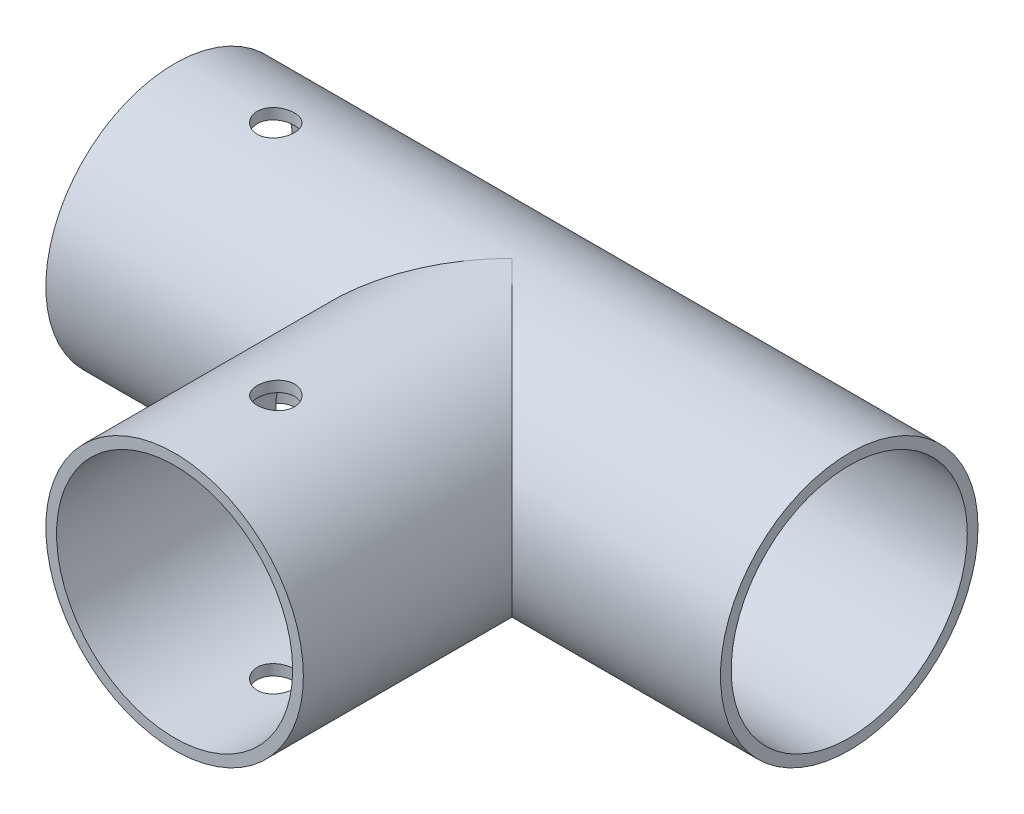
SolidWorks part; units mm, degrees
material "1060 Alloy"
ref_plane "Front Plane" through (0, 0, 0) normal (0, 0, 1) x (1, 0, 0)
ref_plane "Top Plane" through (0, 0, 0) normal (0, 1, 0) x (1, 0, 0)
ref_plane "Right Plane" through (0, 0, 0) normal (1, 0, 0) x (0, 0, -1)
sketch "Sketch1" plane through (0, 0, 0) normal (0, 1, 0) x (1, 0, 0)
  line L0 (0, 0) -> (100, 0) construction
  line L1 (50, 0) -> (50, -50) construction
  dimension "D1" = 100
  dimension "D2" = 50
  dimension "D3" = 90
ref_plane "Plane1" through (0, 0, 0) normal (1, 0, 0) x (0, 0, -1)
sketch "Sketch2" plane through (0, 0, 0) normal (1, 0, 0) x (0, 0, -1)
  circle A0 centre (0, 0) radius 19.0875
  dimension "D1" = 38.175
extrude "Boss-Extrude1" add sketch "Sketch2" along normal up to vertex (100 mm away) up to point (100, 0, 0)
ref_plane "Plane2" through (50, 0, 50) normal (0, 0, 1) x (1, 0, 0)
sketch "Sketch3" plane through (50, 0, 50) normal (0, 0, 1) x (1, 0, 0)
  line L0 (-50, 0) -> (50, 0) construction
  circle A0 centre (0, 0) radius 19.0875
  dimension "D1" = 38.175
extrude "Boss-Extrude2" add sketch "Sketch3" against normal up to surface (30.9125 mm away) up to face at (100, 0, -19.0875)
shell "Shell1" thickness 1.5875 removed face at (100, 0, -19.0875) removed face at (69.0875, 0, 50) removed face at (0, 0, -19.0875)
sketch "Sketch4" plane through (0, 0, 0) normal (0, 1, 0) x (1, 0, 0)
  line L0 (0, 0) -> (15, 0) construction
  line L1 (50, -50) -> (50, -35) construction
  line L2 (30.9125, -50) -> (69.0875, -50) construction
  dimension "D1" = 15
  dimension "D2" = 15
hole_wizard "M5 Clearance Hole1" positions "Sketch5" profile "Sketch6" hole size "M5" standard "AS" end condition through all
sketch "Sketch5" plane through (0, 0, 0) normal (0, 1, 0) x (1, 0, 0)
  point P0 (50, -35)
  point P3 (15, 0)
sketch "Sketch6" plane through (50, 0, 35) normal (1, 0, 0) x (0, 0, -1)
  line L0 (0, 0) -> (0, 19.0875)
  line L1 (0, 19.0875) -> (2.75, 19.0875)
  line L2 (2.75, 19.0875) -> (2.75, 0)
  line L5 (2.75, 0) -> (0, 0)
  line L11 (0, -6.35) -> (0, 107.95) construction
  dimension "Thru Hole Dia." = 5.5
  dimension "Thru Hole Depth" = 19.0875
mirror "Mirror1" about plane through (0, 0, 0) normal (0, 1, 0) of "M5 Clearance Hole1"
equation "\"frontTubeLength\"= 1200mm"
equation "\"outDiameter\"= 35mm"
equation "\"keelOutDiameter\"= 1in"
equation "\"D1@Sketch3\"=\"outDiameter\"+0.125in"
equation "\"D1@Sketch2\"=\"outDiameter\"+0.125in"
